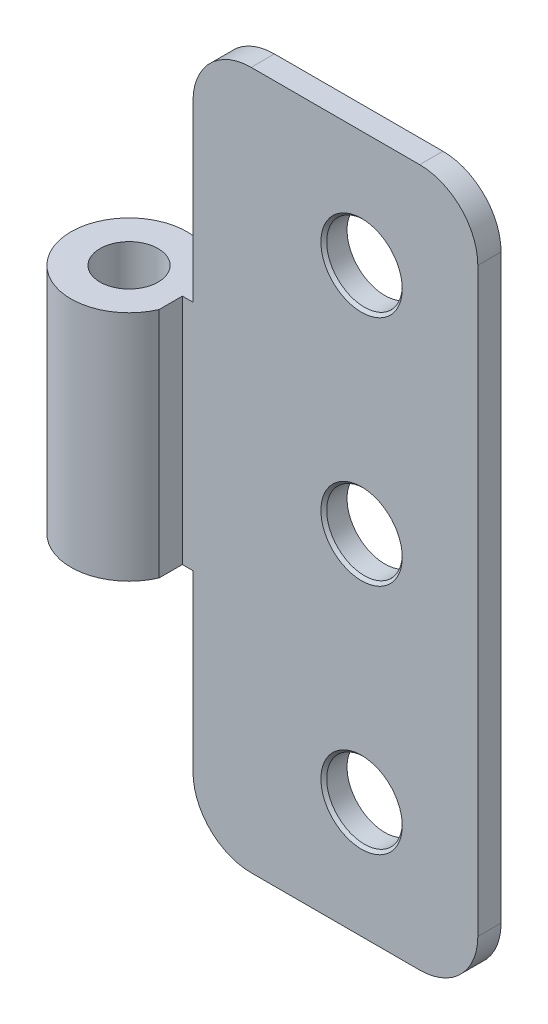
SolidWorks part; units mm, degrees
material "AISI 316 Stainless Steel Sheet (SS)"
ref_plane "Front Plane" through (0, 0, 0) normal (0, 0, 1) x (1, 0, 0)
ref_plane "Top Plane" through (0, 0, 0) normal (0, 1, 0) x (1, 0, 0)
ref_plane "Right Plane" through (0, 0, 0) normal (1, 0, 0) x (0, 0, -1)
sketch "Sketch1" plane through (0, 0, 0) normal (0, 1, 0) x (1, 0, 0)
  line L0 (0, 0) -> (31.9054, 0) construction
  line L1 (30, 2) -> (30, -2)
  line L2 (30, -2) -> (4.5826, -2)
  line L3 (5.5, 2) -> (5.5, -2)
  line L4 (4.5826, -2) -> (4.5826, 0)
  line L5 (30, 2) -> (4.5826, 2)
  line L6 (4.5826, 0) -> (5.5, 0)
  circle A0 centre (0, 0) radius 2.5
  arc A1 (4.5826, 2) -> (4.5826, -2) centre (0, 0) ccw
  dimension "D1" = 4
  dimension "D3" = 5
  dimension "D4" = 10
  dimension "D5" = 30
  dimension "D6" = 5.5
extrude "Boss-Extrude1" add sketch "Sketch1" along normal mid plane 60 contours L3 L0 L1 L5 region at (17.75, 0, -1)
extrude "Boss-Extrude2" add sketch "Sketch1<4>" along normal mid plane 20 contours A0 L3 L5 A1 L2 region at (5.355, 0, -1)
sketch "Sketch1<4>" plane through (0, 0, 0) normal (0, 1, 0) x (1, 0, 0) same geometry as "Sketch1"
hole_wizard "Ø6.5 (6.5) Diameter Hole1" positions "Sketch2" profile "Sketch3" hole size "Ø6.5" standard "ANSI Metric" end condition through all
sketch "Sketch2" plane through (0, 0, 0) normal (0, 0, -1) x (-1, 0, 0)
  line L0 (-20, -30) -> (-20, 30) construction
  line L4 (-5.5, -30) -> (-30, -30) construction
  point P0 (-20, -20)
  point P2 (-20, 0)
  point P4 (-20, 20)
  dimension "D1" = 20
  dimension "D2" = 20
  dimension "D3" = 20
sketch "Sketch3" plane through (20, -20, 0) normal (1, 0, 0) x (0, -1, 0)
  line L0 (0, 0) -> (0, 5)
  line L1 (0, 5) -> (3.25, 5)
  line L2 (3.25, 5) -> (3.25, 0.25)
  line L3 (3.25, 0.25) -> (3.5, 0)
  line L5 (3.5, 0) -> (0, 0)
  line L6 (-3.25, 0.25) -> (-3.5, 0) construction
  line L11 (0, -6.35) -> (0, 107.95) construction
  dimension "Thru Hole Dia." = 6.5
  dimension "Thru Hole Depth" = 5
  dimension "Near C'Sink Dia." = 7
  dimension "Near C'Sink Angle" = 90
fillet "Fillet1" radius 5 4 edges at (30, 30, -1) (30, -30, -1) (5.5, -30, -1) (5.5, 30, -1)
